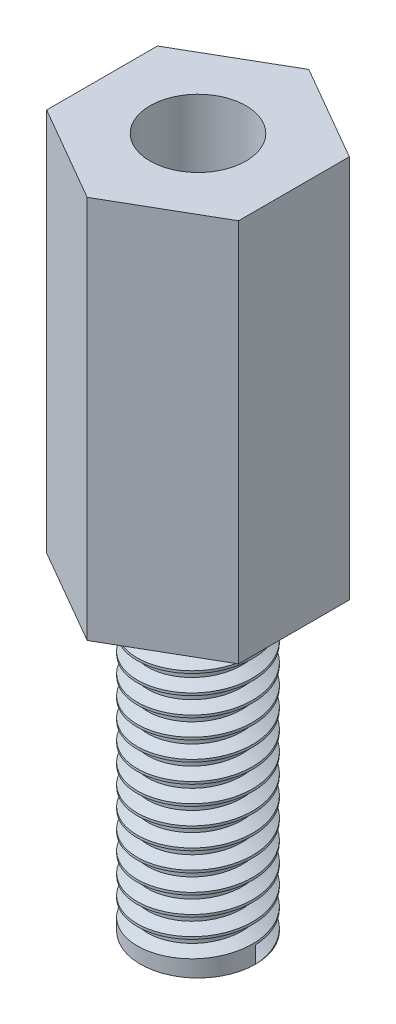
SolidWorks part; units mm, degrees
ref_plane "Front" through (0, 0, 0) normal (0, 0, 1) x (1, 0, 0)
ref_plane "Top" through (0, 0, 0) normal (0, 1, 0) x (1, 0, 0)
ref_plane "Right" through (0, 0, 0) normal (1, 0, 0) x (0, 0, -1)
sketch "Sketch1" plane through (0, 0, 0) normal (0, 0, 1) x (1, 0, 0)
  line L0 (0, 0) -> (0, 18)
  line L1 (0, 18) -> (5, 18)
  line L2 (5, 18) -> (5, 8)
  line L3 (5, 8) -> (1.5, 8)
  line L4 (1.5, 8) -> (1.5, 0)
  line L5 (1.5, 0) -> (0, 0)
  point P3 (0.75, 0)
  dimension "D1" = 1.5
  dimension "D2" = 5
  dimension "D3" = 10
  dimension "D4" = 8
revolve "Revolve1" add sketch "Sketch1" angle 360 about L0
sketch "Sketch2" plane through (0, 0, 0) normal (0, 1, 0) x (1, 0, 0)
  line L0 (0, -2.8868) -> (-2.5, -1.4434)
  line L1 (-2.5, -1.4434) -> (-2.5, 1.4434)
  line L2 (-2.5, 1.4434) -> (0, 2.8868)
  line L3 (0, 2.8868) -> (2.5, 1.4434)
  line L4 (2.5, 1.4434) -> (2.5, -1.4434)
  line L5 (2.5, -1.4434) -> (0, -2.8868)
  line L6 (0, 2.8868) -> (0, -2.8868) construction
  point P2 (0, 0)
  point P7 (-2.6635, -1.7528)
  point P8 (-2.5107, 1.4127)
  point P10 (0, 2.8868)
  dimension "D1" = 120
  dimension "D2" = 5
  dimension "D3" = 60
extrude "Cut-Extrude2" cut sketch "Sketch2" against normal through all and the other way through all flip side to cut
thread "Thread1" pitch 0.5 method cut profile "Thread Profile1" start angle 0, offset 0, length 0, pitch 0.5, diameter 3
ref_plane "Plane1" through (1.5, 0, 0) normal (0, 0, 1) x (1, 0, 0)
sketch "Thread Profile1" plane through (1.5, 0, 0) normal (0, 0, 1) x (1, 0, 0)
  line L0 (0, 0) -> (0, 0.5) construction
  line L11 (0, 0) -> (0, 0.4375)
  line L12 (0, 0.4375) -> (-0.2706, 0.2812)
  line L13 (-0.2706, 0.2812) -> (-0.2706, 0.1562)
  line L15 (-0.2706, 0.1562) -> (0, 0)
  line L17 (-0.2706, 0.2187) -> (0, 0.2187) construction
  point P2 (0, 0)
  dimension "Pitch" = 0.5
  dimension "Profile_Angle" = 60
  dimension "Profile_Land" = 0.125
  dimension "Profile_Height" = 0.2706
hole_wizard "M3 Tapped Hole1" positions "Sketch7" profile "Sketch8" tap size "M3" standard "DIN"
sketch "Sketch7" plane through (0, 18, 18) normal (0, 1, 0) x (1, 0, 0)
  point P1 (0, 18)
  point P6 (0, 0)
  point P7 (-0.0485, 17.9272)
  point P8 (0, 18)
sketch "Sketch8" plane through (0, 18, 0) normal (1, 0, 0) x (0, 0, 1)
  line L0 (0, 0) -> (0, 10.2511)
  line L1 (0, 10.2511) -> (1.25, 9.5)
  line L2 (1.25, 9.5) -> (1.25, 0)
  line L5 (1.25, 0) -> (0, 0)
  line L10 (0, 10.2511) -> (-1.25, 9.5) construction
  line L11 (0, -6.35) -> (0, 107.95) construction
  dimension "Tap Drill Dia." = 2.5
  dimension "Tap Drill Depth" = 9.5
  dimension "Drill Angle" = 118
cosmetic thread "Hole Thread3" parameters "D1"=8, "D2"=3
